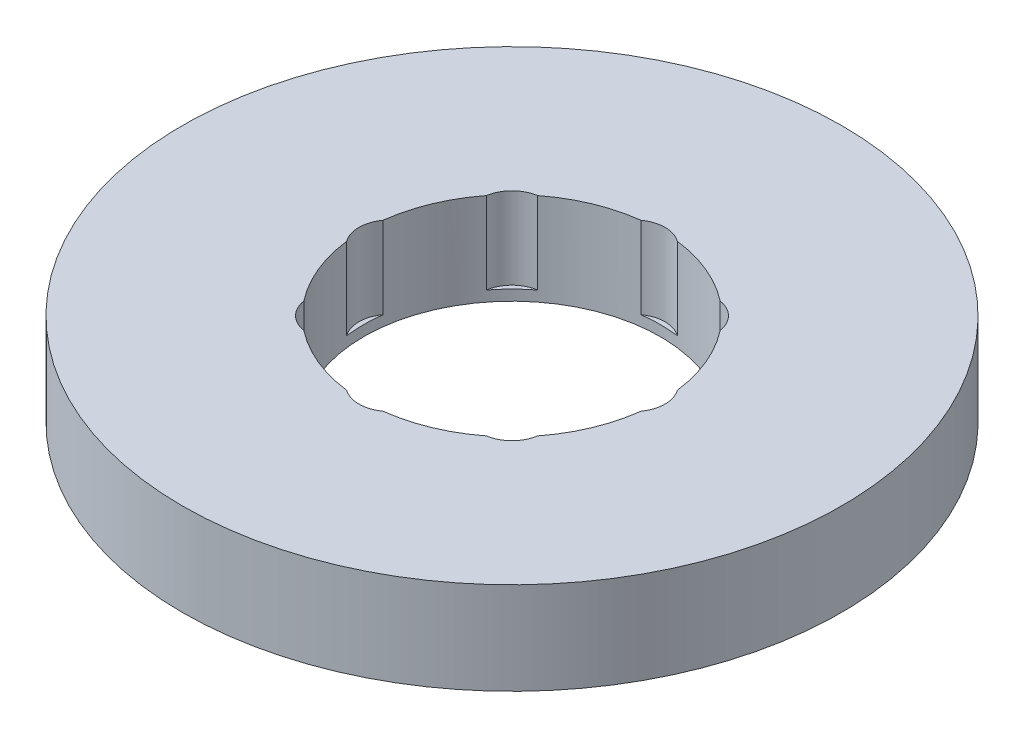
SolidWorks part; units mm, degrees
ref_plane "Front Plane" through (0, 0, 0) normal (0, 0, 1) x (1, 0, 0)
ref_plane "Top Plane" through (0, 0, 0) normal (0, 1, 0) x (1, 0, 0)
ref_plane "Right Plane" through (0, 0, 0) normal (1, 0, 0) x (0, 0, -1)
sketch "Sketch1" plane through (0, 0, 0) normal (0, 1, 0) x (1, 0, 0)
  circle A0 centre (0, 0) radius 100
  dimension "FLANGE_OD" = 200
extrude "Boss-Extrude1" add sketch "Sketch1" along normal blind 28
sketch "Sketch2" plane through (0, 0, 0) normal (0, 1, 0) x (1, 0, 0)
  circle A0 centre (0, 0) radius 45
  dimension "BORE_D" = 90
extrude "Cut-Extrude1" cut sketch "Sketch2" along normal through all
sketch "Sketch3" plane through (0, 28, 0) normal (0, 1, 0) x (1, 0, 0)
  circle A0 centre (0, 0) radius 37.04 construction
  circle A1 centre (-37.04, 0) radius 9.4039
  dimension "BOLT_D" = 18.8079
  dimension "BOLT_PCD" = 74.08
extrude "Cut-Extrude2" cut sketch "Sketch3" against normal blind 24.8115
pattern_circular "CirPattern1" count 8 over 360 about axis through (0, 0, 0) along (0, 1, 0) of "Cut-Extrude2"
